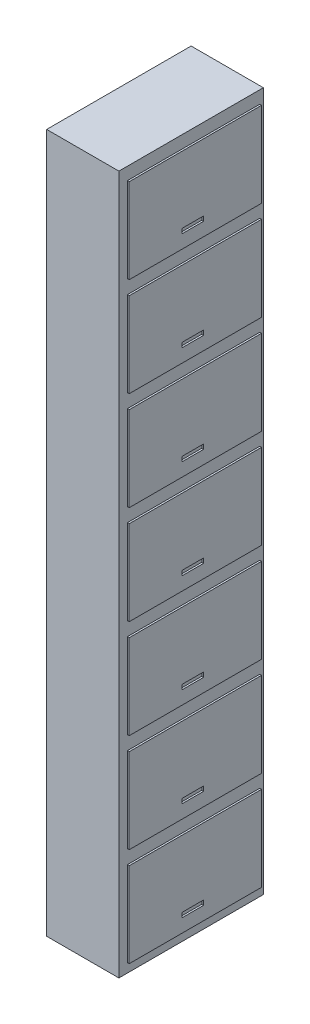
SolidWorks part; units mm, degrees
ref_plane "Front Plane" through (0, 0, 0) normal (0, 0, 1) x (1, 0, 0)
ref_plane "Top Plane" through (0, 0, 0) normal (0, 1, 0) x (1, 0, 0)
ref_plane "Right Plane" through (0, 0, 0) normal (1, 0, 0) x (0, 0, -1)
sketch "Sketch1" plane through (0, 0, 0) normal (0, 0, 1) x (1, 0, 0)
  line L0 (263.062, 4179.9863) -> (-136.938, 4179.9863)
  line L1 (-136.938, 4179.9863) -> (-136.938, 309.9863)
  line L2 (-136.938, 309.9863) -> (263.062, 309.9863)
  line L5 (263.062, 309.9863) -> (263.062, 4179.9863)
  dimension "D1" = 400
  dimension "D2" = 3870
extrude "Boss-Extrude1" add sketch "Sketch1" along normal blind 800
sketch "Sketch3" plane through (263.062, 0, 0) normal (1, 0, 0) x (0, 0, -1)
  line L1 (-752.8351, 359.9863) -> (-20, 359.9863)
  line L2 (-752.8351, 359.9863) -> (-752.8351, 829.9863)
  line L3 (-752.8351, 829.9863) -> (-20, 829.9863)
  line L4 (-20, 359.9863) -> (-20, 829.9863)
  line L5 (-800, 309.9863) -> (0, 309.9863) construction
  line L6 (-752.8351, 906.7588) -> (-20, 906.7588)
  line L7 (-461.6648, -2274.1108) -> (-340.5919, -2274.1108)
  line L8 (-461.6648, -2274.1108) -> (-461.6648, -2299.9132)
  line L9 (-461.6648, -2299.9132) -> (-340.5919, -2299.9132)
  line L10 (-340.5919, -2274.1108) -> (-340.5919, -2299.9132)
  line L11 (-752.8351, 906.7588) -> (-752.8351, 1376.7588)
  line L12 (-752.8351, 1376.7588) -> (-20, 1376.7588)
  line L13 (-20, 906.7588) -> (-20, 1376.7588)
  line L14 (-461.6648, -1727.3383) -> (-340.5919, -1727.3383)
  line L15 (-461.6648, -1753.1407) -> (-340.5919, -1753.1407)
  line L16 (-461.6648, -1727.3383) -> (-461.6648, -1753.1407)
  line L17 (-340.5919, -1727.3383) -> (-340.5919, -1753.1407)
  line L18 (-752.8351, 1453.5313) -> (-20, 1453.5313)
  line L19 (-752.8351, 1453.5313) -> (-752.8351, 1923.5313)
  line L20 (-752.8351, 1923.5313) -> (-20, 1923.5313)
  line L21 (-20, 1453.5313) -> (-20, 1923.5313)
  line L26 (-752.8351, 2000.3038) -> (-20, 2000.3038)
  line L27 (-752.8351, 2000.3038) -> (-752.8351, 2470.3038)
  line L28 (-752.8351, 2470.3038) -> (-20, 2470.3038)
  line L29 (-20, 2000.3038) -> (-20, 2470.3038)
  line L36 (-752.8351, 2547.0763) -> (-20, 2547.0763)
  line L37 (-752.8351, 2547.0763) -> (-752.8351, 3017.0763)
  line L38 (-752.8351, 3017.0763) -> (-20, 3017.0763)
  line L39 (-20, 2547.0763) -> (-20, 3017.0763)
  line L44 (-752.8351, 3093.8488) -> (-20, 3093.8488)
  line L45 (-752.8351, 3093.8488) -> (-752.8351, 3563.8488)
  line L46 (-752.8351, 3563.8488) -> (-20, 3563.8488)
  line L47 (-20, 3093.8488) -> (-20, 3563.8488)
  line L48 (-461.6648, 459.7517) -> (-340.5919, 459.7517)
  line L49 (-461.6648, 433.9492) -> (-340.5919, 433.9492)
  line L50 (-461.6648, 459.7517) -> (-461.6648, 433.9492)
  line L51 (-340.5919, 459.7517) -> (-340.5919, 433.9492)
  line L52 (-752.8351, 3640.6212) -> (-20, 3640.6212)
  line L53 (-752.8351, 3640.6212) -> (-752.8351, 4110.6212)
  line L54 (-752.8351, 4110.6212) -> (-20, 4110.6212)
  line L55 (-20, 3640.6212) -> (-20, 4110.6212)
  line L56 (-461.6648, 1006.5241) -> (-340.5919, 1006.5241)
  line L57 (-461.6648, 980.7217) -> (-340.5919, 980.7217)
  line L58 (-461.6648, 1006.5241) -> (-461.6648, 980.7217)
  line L59 (-340.5919, 1006.5241) -> (-340.5919, 980.7217)
  line L64 (-461.6648, 1553.2966) -> (-340.5919, 1553.2966)
  line L65 (-461.6648, 1527.4942) -> (-340.5919, 1527.4942)
  line L66 (-461.6648, 1553.2966) -> (-461.6648, 1527.4942)
  line L67 (-340.5919, 1553.2966) -> (-340.5919, 1527.4942)
  line L72 (-461.6648, 2100.0691) -> (-340.5919, 2100.0691)
  line L73 (-461.6648, 2074.2667) -> (-340.5919, 2074.2667)
  line L74 (-461.6648, 2100.0691) -> (-461.6648, 2074.2667)
  line L75 (-340.5919, 2100.0691) -> (-340.5919, 2074.2667)
  line L80 (-461.6648, 2646.8416) -> (-340.5919, 2646.8416)
  line L81 (-461.6648, 2621.0392) -> (-340.5919, 2621.0392)
  line L82 (-461.6648, 2646.8416) -> (-461.6648, 2621.0392)
  line L83 (-340.5919, 2646.8416) -> (-340.5919, 2621.0392)
  line L88 (-461.6648, 3193.6141) -> (-340.5919, 3193.6141)
  line L89 (-461.6648, 3167.8117) -> (-340.5919, 3167.8117)
  line L90 (-461.6648, 3193.6141) -> (-461.6648, 3167.8117)
  line L91 (-340.5919, 3193.6141) -> (-340.5919, 3167.8117)
  line L96 (-461.6648, 3740.3866) -> (-340.5919, 3740.3866)
  line L97 (-461.6648, 3714.5842) -> (-340.5919, 3714.5842)
  line L98 (-461.6648, 3740.3866) -> (-461.6648, 3714.5842)
  line L99 (-340.5919, 3740.3866) -> (-340.5919, 3714.5842)
  line L116 (-752.8351, 4734.1662) -> (-752.8351, 5204.1662) [skipped]
  line L117 (-752.8351, 5204.1662) -> (-20, 5204.1662) [skipped]
  line L118 (-20, 4734.1662) -> (-20, 5204.1662) [skipped]
  line L119 (-752.8351, 5280.9387) -> (-20, 5280.9387) [skipped]
  line L120 (-752.8351, 5280.9387) -> (-752.8351, 5750.9387) [skipped]
  line L121 (-752.8351, 5750.9387) -> (-20, 5750.9387) [skipped]
  line L122 (-20, 5280.9387) -> (-20, 5750.9387) [skipped]
  line L123 (-752.8351, 5827.7112) -> (-20, 5827.7112) [skipped]
  line L124 (-752.8351, 5827.7112) -> (-752.8351, 6297.7112) [skipped]
  line L125 (-752.8351, 6297.7112) -> (-20, 6297.7112) [skipped]
  line L126 (-20, 5827.7112) -> (-20, 6297.7112) [skipped]
  line L127 (-752.8351, 6374.4837) -> (-20, 6374.4837) [skipped]
  line L128 (-752.8351, 6374.4837) -> (-752.8351, 6844.4837) [skipped]
  line L129 (-752.8351, 6844.4837) -> (-20, 6844.4837) [skipped]
  line L130 (-20, 6374.4837) -> (-20, 6844.4837) [skipped]
  line L131 (-752.8351, 6921.2562) -> (-20, 6921.2562) [skipped]
  line L132 (-752.8351, 6921.2562) -> (-752.8351, 7391.2562) [skipped]
  line L133 (-752.8351, 7391.2562) -> (-20, 7391.2562) [skipped]
  line L134 (-20, 6921.2562) -> (-20, 7391.2562) [skipped]
  line L135 (-752.8351, 7468.0286) -> (-20, 7468.0286) [skipped]
  line L136 (-752.8351, 7468.0286) -> (-752.8351, 7938.0286) [skipped]
  line L137 (-752.8351, 7938.0286) -> (-20, 7938.0286) [skipped]
  line L138 (-20, 7468.0286) -> (-20, 7938.0286) [skipped]
  line L139 (-752.8351, 4187.3937) -> (-752.8351, 4657.3937) [skipped]
  line L140 (-752.8351, 4657.3937) -> (-20, 4657.3937) [skipped]
  line L141 (-20, 4187.3937) -> (-20, 4657.3937) [skipped]
  line L142 (-752.8351, 4734.1662) -> (-20, 4734.1662) [skipped]
  line L143 (-461.6648, 4833.9315) -> (-340.5919, 4833.9315) [skipped]
  line L144 (-461.6648, 4808.1291) -> (-340.5919, 4808.1291) [skipped]
  line L145 (-461.6648, 4833.9315) -> (-461.6648, 4808.1291) [skipped]
  line L146 (-340.5919, 4833.9315) -> (-340.5919, 4808.1291) [skipped]
  line L147 (-752.8351, 4187.3937) -> (-20, 4187.3937) [skipped]
  line L148 (-461.6648, 4287.1591) -> (-340.5919, 4287.1591) [skipped]
  line L149 (-461.6648, 4261.3567) -> (-340.5919, 4261.3567) [skipped]
  line L150 (-461.6648, 4287.1591) -> (-461.6648, 4261.3567) [skipped]
  line L151 (-340.5919, 4287.1591) -> (-340.5919, 4261.3567) [skipped]
  line L152 (-461.6648, -1180.5658) -> (-340.5919, -1180.5658) [skipped]
  line L153 (-461.6648, -1206.3682) -> (-340.5919, -1206.3682) [skipped]
  line L154 (-461.6648, -1180.5658) -> (-461.6648, -1206.3682) [skipped]
  line L155 (-340.5919, -1180.5658) -> (-340.5919, -1206.3682) [skipped]
  line L156 (-461.6648, -633.7933) -> (-340.5919, -633.7933) [skipped]
  line L157 (-461.6648, -659.5957) -> (-340.5919, -659.5957) [skipped]
  line L158 (-461.6648, -633.7933) -> (-461.6648, -659.5957) [skipped]
  line L159 (-340.5919, -633.7933) -> (-340.5919, -659.5957) [skipped]
  line L160 (-461.6648, -87.0208) -> (-340.5919, -87.0208) [skipped]
  line L161 (-461.6648, -112.8232) -> (-340.5919, -112.8232) [skipped]
  line L162 (-461.6648, -87.0208) -> (-461.6648, -112.8232) [skipped]
  line L163 (-340.5919, -87.0208) -> (-340.5919, -112.8232) [skipped]
  dimension "D1" = 470
  dimension "D3" = 50
  dimension "D4" = 14
extrude "Boss-Extrude3" add sketch "Sketch3" along normal blind 10 contours L1 L4 L3 L2 L7 L10 L9 L8 | L18 L21 L20 L19 | L6 L13 L12 L11 L14 L17 L15 L16 | L26 L29 L28 L27 | L36 L39 L38 L37 | L44 L47 L46 L45 L48 L51 L49 L50 | L52 L55 L54 L53 L56 L59 L57 L58 | L64 L67 L65 L66 | L72 L75 L73 L74 | L80 L83 L81 L82 | L88 L91 L89 L90 | L96 L99 L97 L98 region at (263.062, 596.3422, 386.2829) region at (263.062, 1143.1147, 386.2829) region at (263.062, 1689.8872, 386.2829) region at (263.062, 2236.6597, 386.2829) region at (263.062, 2783.4321, 386.2829) region at (263.062, 3330.2046, 386.2829) region at (263.062, 3876.9771, 386.2829)
